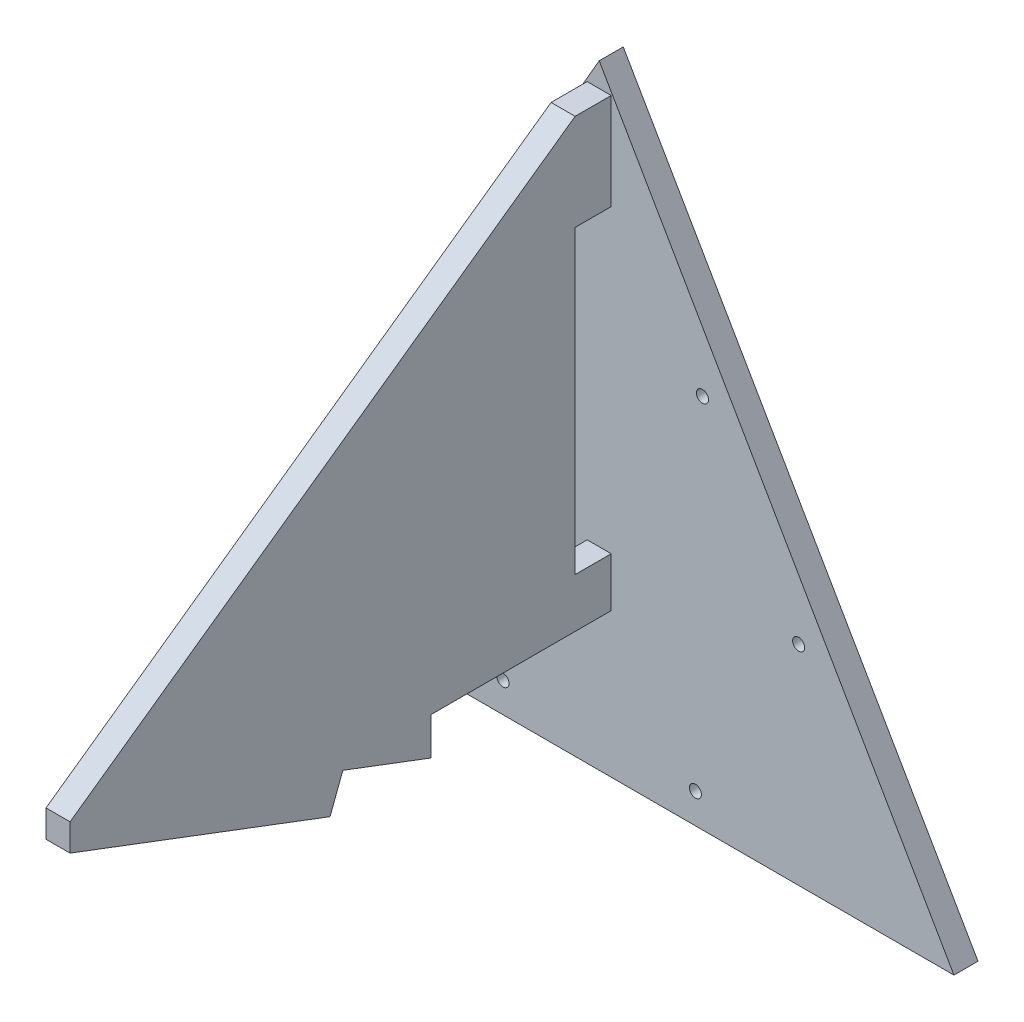
SolidWorks part; units mm, degrees
ref_plane "Front Plane" through (0, 0, 0) normal (0, 0, 1) x (1, 0, 0)
ref_plane "Top Plane" through (0, 0, 0) normal (0, 1, 0) x (1, 0, 0)
ref_plane "Right Plane" through (0, 0, 0) normal (1, 0, 0) x (0, 0, -1)
sketch "Sketch1" plane through (0, 0, 0) normal (0, 0, 1) x (1, 0, 0)
  line L0 (0, 34.0637) -> (-29.5, -17.0318)
  line L1 (-29.5, -17.0318) -> (29.5, -17.0318)
  line L2 (29.5, -17.0318) -> (0, 34.0637)
  line L3 (0, 34.0637) -> (0, -17.0318) construction
  line L4 (-14.75, 8.5159) -> (29.5, -17.0318) construction
  point P4 (0, 0)
  dimension "D1" = 59
extrude "Boss-Extrude1" add sketch "Sketch1" along normal blind 2
sketch "Sketch2" plane through (0, 0, 0) normal (1, 0, 0) x (0, 0, -1)
  line L0 (0, 0) -> (50000, 0) construction
  line L1 (-2, -0.9363) -> (-2, -5.0318)
  line L2 (-2, -17.0318) -> (-2, 34.0637) construction
  line L3 (-2, -5.0318) -> (-17, -5.0318)
  line L4 (-17, -5.0318) -> (-17, -8.1469)
  line L5 (-17, -8.1469) -> (-24.3194, -5.3766)
  line L6 (-24.3194, -5.3766) -> (-25.3813, -8.1823)
  line L7 (-25.3813, -8.1823) -> (-47, 0)
  line L8 (-2, 32.0637) -> (-5, 32.0637)
  line L9 (-5, 32.0637) -> (-47, 2.2599)
  line L10 (-47, 2.2599) -> (-47, 0)
  line L11 (-2, 32.0637) -> (-2, 24.0637)
  line L12 (-2, 24.0637) -> (-5, 24.0637)
  line L13 (-5, 24.0637) -> (-5, -0.9363)
  line L14 (-5, -0.9363) -> (-2, -0.9363)
  dimension "D1" = 15
  dimension "D2" = 3
  dimension "D3" = 45
  dimension "D4" = 12
  dimension "D5" = 25
  dimension "D6" = 3
  dimension "D7" = 35.36
  dimension "D8" = 2
  dimension "D9" = 8
  dimension "D10" = 3
  dimension "D11" = 25
extrude "Boss-Extrude2" add sketch "Sketch2" along normal mid plane 2
sketch "Sketch3" plane through (0, 0, 2) normal (0, 0, 1) x (1, 0, 0)
  line L0 (0, -1017.0318) -> (0, 48982.9682) construction
  line L1 (-29.5, -17.0318) -> (29.5, -17.0318) construction
  circle A0 centre (-8, -14.5318) radius 0.5
  circle A1 centre (8, -14.5318) radius 0.5
  point P5 (0, -17.0318)
  dimension "D1" = 1
  dimension "D2" = 8
  dimension "D3" = 2.5
extrude "Cut-Extrude1" cut sketch "Sketch3" against normal through all
ref_axis "Axis1" through (0, 0, -2.35) along (0, 0, 1)
pattern_circular "CirPattern1" count 3 over 360 about axis through (0, 0, -2.35) along (0, 0, 1) of "Cut-Extrude1"
